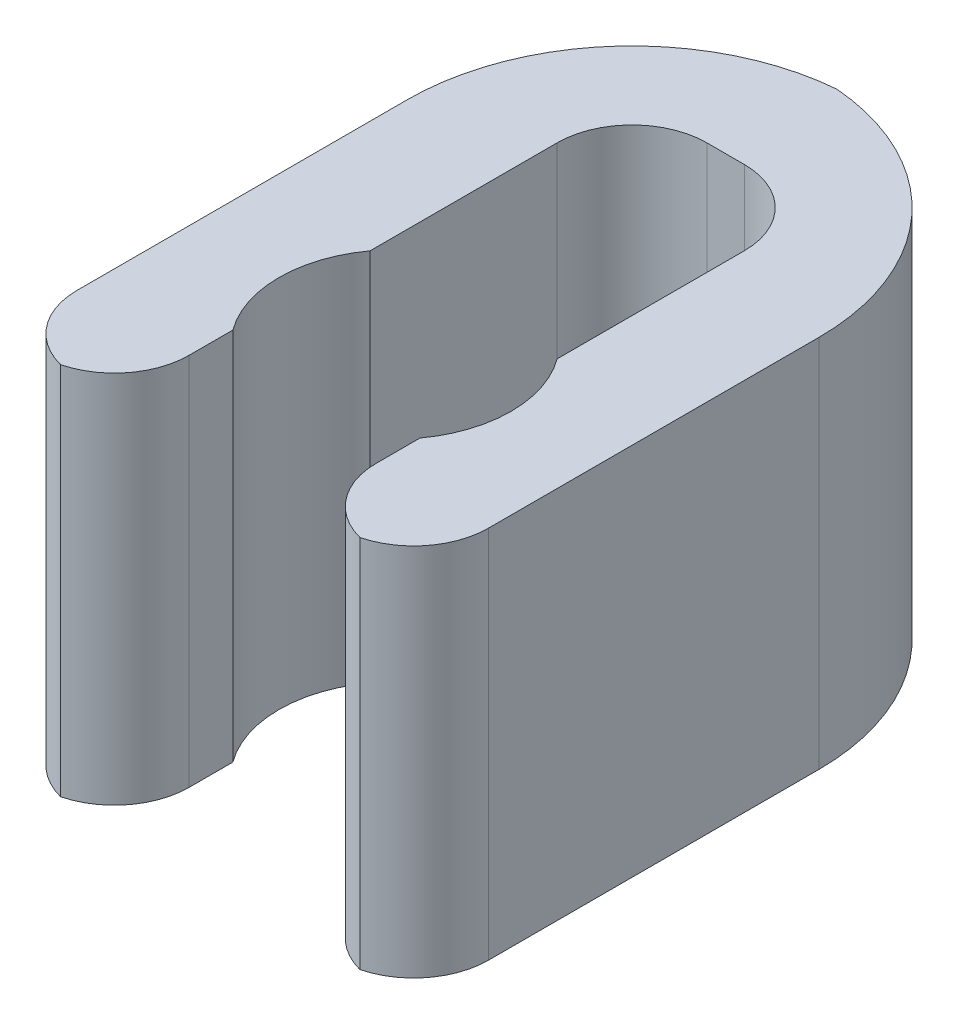
SolidWorks part; units mm, degrees
ref_plane "Front Plane" through (0, 0, 0) normal (0, 0, 1) x (1, 0, 0)
ref_plane "Top Plane" through (0, 0, 0) normal (0, 1, 0) x (1, 0, 0)
ref_plane "Right Plane" through (0, 0, 0) normal (1, 0, 0) x (0, 0, -1)
sketch "Sketch1" plane through (0, 0, 0) normal (0, 1, 0) x (1, 0, 0)
  line L0 (-27.1712, -6.1809) -> (-27.1712, -9.3479)
  line L1 (-27.1712, -2.5149) -> (-22.1712, -2.5149)
  line L2 (-27.1712, -2.5149) -> (-27.1712, 4.4851)
  line L3 (-27.1712, 4.4851) -> (-22.1712, 4.4851)
  line L4 (-22.1712, -2.5149) -> (-22.1712, 4.4851)
  line L5 (-30.1712, 7.4851) -> (-19.1712, 7.4851)
  line L6 (-30.1712, 7.4851) -> (-30.1712, -9.3479)
  line L7 (-30.1712, -9.3479) -> (-19.1712, -9.3479)
  line L8 (-19.1712, 7.4851) -> (-19.1712, -9.3479)
  line L9 (-22.1712, -6.1809) -> (-22.1712, -9.3479)
  circle A0 centre (-24.6712, -4.3479) radius 3.1
  dimension "D1" = 6.2
  dimension "D2" = 5
  dimension "D3" = 7
  dimension "D4" = 3
  dimension "D5" = 3
  dimension "D6" = 3
  dimension "D7" = 5
  dimension "D8" = 5.5
extrude "Boss-Extrude1" add sketch "Sketch1" along normal blind 10 contours A0 L9 L7 L8 L5 L6 L0 L2 L3 L4 region at (-27.3723, 0, 7.7644)
fillet "Fillet1" radius 6 2 edges at (-19.1712, 5, -7.4851) (-30.1712, 5, -7.4851)
fillet "Fillet2" radius 2 4 edges at (-19.1712, 5, 9.3479) (-22.1712, 5, 9.3479) (-27.1712, 5, 9.3479) (-30.1712, 5, 9.3479)
fillet "Fillet3" radius 2 2 edges at (-27.1712, 5, -4.4851) (-22.1712, 5, -4.4851)
